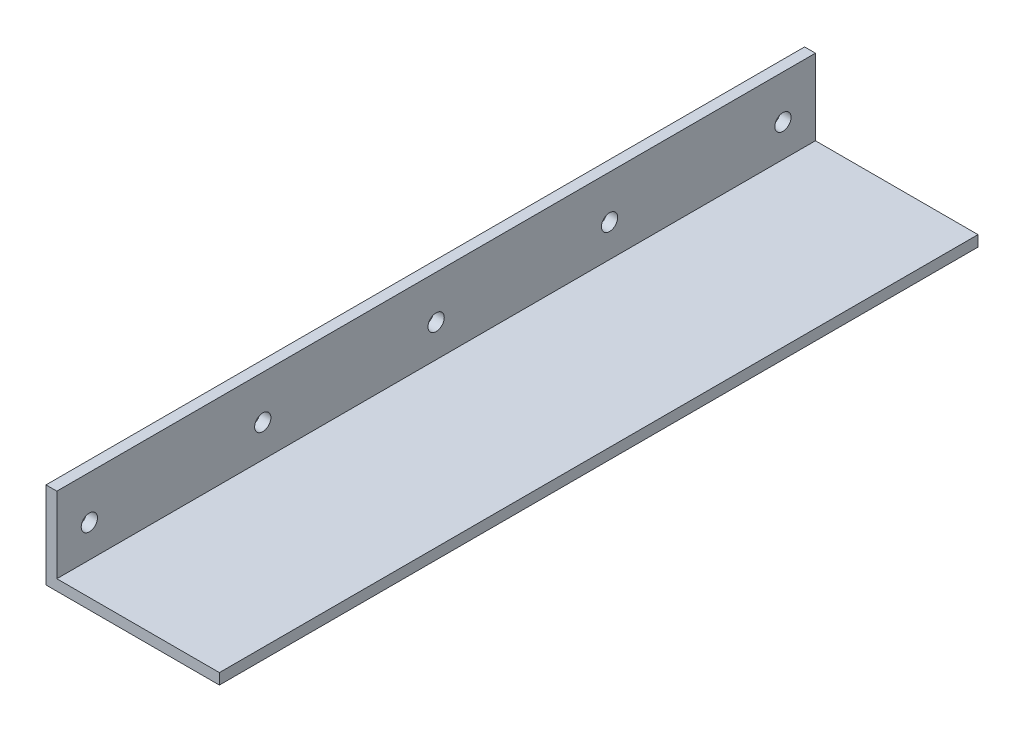
SolidWorks part; units mm, degrees
material "6063-T1"
ref_plane "Front Plane" through (0, 0, 0) normal (0, 0, 1) x (1, 0, 0)
ref_plane "Top Plane" through (0, 0, 0) normal (0, 1, 0) x (1, 0, 0)
ref_plane "Right Plane" through (0, 0, 0) normal (1, 0, 0) x (0, 0, -1)
sketch "Sketch1" plane through (0, 0, 0) normal (0, 0, 1) x (1, 0, 0)
  line L1 (0, 0) -> (50.8, 0)
  line L2 (0, 0) -> (0, 25.4)
  line L3 (0, 25.4) -> (50.8, 25.4)
  line L4 (50.8, 0) -> (50.8, 25.4)
  line L5 (50.8, 25.4) -> (3.175, 25.4)
  line L6 (50.8, 25.4) -> (50.8, 3.175)
  line L7 (50.8, 3.175) -> (3.175, 3.175)
  line L8 (3.175, 25.4) -> (3.175, 3.175)
  dimension "D1" = 3.175
  dimension "D2" = 3.175
  dimension "D3" = 25.4
  dimension "D4" = 50.8
extrude "Boss-Extrude1" add sketch "Sketch1" along normal blind 222.25 contours L8 L3 L2 L1 L4 L7 region at (0.568, 12.7, 0)
sketch "Sketch2" plane through (0, 0, 0) normal (-1, 0, 0) x (0, 0, 1)
  line L0 (222.25, 0) -> (0, 0) construction
  line L1 (222.25, 0) -> (222.25, 25.4) construction
  circle A0 centre (212.725, 12.7) radius 2.3813
  circle A1 centre (161.925, 12.7) radius 2.3813
  circle A2 centre (111.125, 12.7) radius 2.3813
  circle A3 centre (60.325, 12.7) radius 2.3813
  circle A4 centre (9.525, 12.7) radius 2.3813
  circle A5 centre (-41.275, 12.7) radius 2.3813
  circle A6 centre (-92.075, 12.7) radius 2.3813
  circle A7 centre (-142.875, 12.7) radius 2.3813
  circle A8 centre (-193.675, 12.7) radius 2.3813
  circle A9 centre (-244.475, 12.7) radius 2.3813
  dimension "D3" = 4.7625
  dimension "D1" = 12.7
  dimension "D2" = 9.525
  dimension "D4" = 10
extrude "Cut-Extrude1" cut sketch "Sketch2" against normal through all
chamfer "Chamfer1" [suppressed] distance 50.8 angle 45
chamfer "Chamfer2" [suppressed] distance 50.8 angle 45
